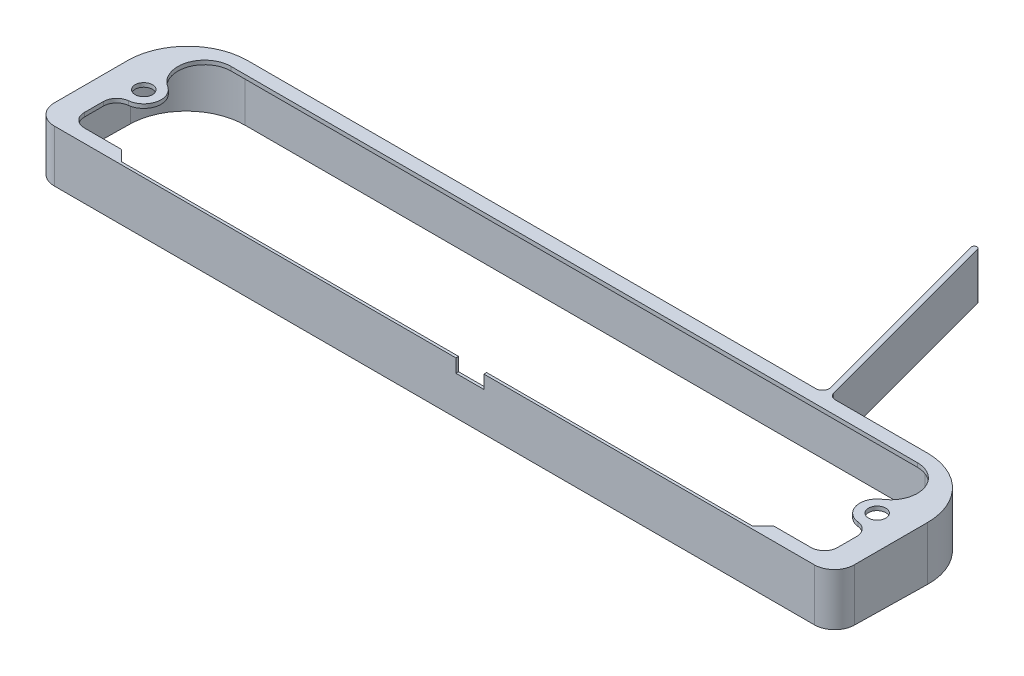
SolidWorks part; units mm, degrees
material "ABS"
ref_plane "Front" through (0, 0, 0) normal (0, 0, 1) x (1, 0, 0)
ref_plane "Top" through (0, 0, 0) normal (0, 1, 0) x (1, 0, 0)
ref_plane "Right" through (0, 0, 0) normal (1, 0, 0) x (0, 0, -1)
ref_axis "X" through (-80.9, 0, 0) along (1, 0, 0)
ref_axis "Y" through (0, -50, 0) along (0, 1, 0)
ref_axis "Z" through (0, 0, -80.9) along (0, 0, 1)
sketch "Sketch1" plane through (0, 0, 0) normal (0, 1, 0) x (1, 0, 0)
  line L0 (-57, 0) -> (-56.5, 0)
  line L2 (-51.4595, 21) -> (51.4595, 21)
  line L4 (56.5, 0) -> (57, 0)
  line L5 (60, 3) -> (60, 14)
  line L6 (51, 23) -> (-51, 23)
  line L7 (-60, 14) -> (-60, 3)
  line L8 (-56.5, 0) -> (56.5, 0)
  line L9 (-49, 0.4) -> (49, 0.4)
  line L10 (-56.5, 0) -> (-56.5, 0.4) construction
  line L11 (56.5, 0) -> (56.5, 0.4) construction
  line L12 (55, 11.43) -> (-55, 11.43) construction
  line L13 (0, 11.43) -> (0, 0) construction
  line L14 (56.5, 2) -> (49, 2)
  line L15 (49, 2) -> (49, 0.4)
  line L16 (-56.5, 2) -> (-49, 2)
  line L17 (-49, 2) -> (-49, 0.4)
  line L18 (-56.5, 0.4) -> (-56.5, 2) construction
  line L19 (-56.5, 0.4) -> (-49, 0.4) construction
  line L20 (56.5, 2) -> (56.5, 0.4) construction
  line L21 (49, 0.4) -> (56.5, 0.4) construction
  line L22 (56.5, 6.8573) -> (56.5, 2)
  line L23 (-56.5, 2) -> (-56.5, 6.8573)
  arc A0 (-53.6053, 13.6242) -> (-51.4595, 21) centre (-51.4595, 17) cw
  arc A1 (51.4595, 21) -> (53.6053, 13.6242) centre (51.4595, 17) cw
  arc A2 (60, 14) -> (51, 23) centre (51, 14) ccw
  arc A3 (-51, 23) -> (-60, 14) centre (-51, 14) ccw
  circle A4 centre (55, 11.43) radius 1.3
  circle A5 centre (-55, 11.43) radius 1.3
  arc A6 (53.6053, 13.6242) -> (54.7174, 8.8454) centre (55, 11.43) ccw
  arc A7 (-53.6053, 13.6242) -> (-54.7174, 8.8454) centre (-55, 11.43) cw
  arc A8 (-54.7174, 8.8454) -> (-56.5, 6.8573) centre (-54.5, 6.8573) ccw
  arc A9 (56.5, 6.8573) -> (54.7174, 8.8454) centre (54.5, 6.8573) ccw
  arc A10 (-57, 0) -> (-60, 3) centre (-57, 3) cw
  arc A11 (60, 3) -> (57, 0) centre (57, 3) cw
  dimension "D5" = 9
  dimension "D6" = 4
  dimension "D10" = 2.6
  dimension "D13" = 2.6
  dimension "D14" = 2
  dimension "D15" = 3
  dimension "D1" = 120
  dimension "D2" = 3.5
  dimension "D3" = 2
  dimension "D4" = 23
  dimension "D7" = 0.4
  dimension "D8" = 11.43
  dimension "D9" = 110
  dimension "D11" = 11
  dimension "D12" = 2
extrude "Boss-Extrude1" add sketch "Sketch1" along normal blind 0.6
sketch "Sketch8" plane through (0, 0, 0) normal (0, -1, 0) x (-1, 0, 0)
  line L4 (51, 22.6) -> (-51, 22.6)
  line L5 (-59.6, 14) -> (-59.6, 3)
  line L12 (-57, 0.4) -> (57, 0.4)
  line L13 (59.6, 3) -> (59.6, 14)
  line L14 (-57, 0) -> (57, 0)
  line L15 (60, 3) -> (60, 14)
  line L16 (51, 23) -> (-51, 23)
  line L17 (-60, 14) -> (-60, 3)
  line L18 (-57, 0) -> (57, 0)
  line L19 (60, 3) -> (60, 14)
  line L20 (51, 23) -> (-51, 23)
  line L21 (-60, 14) -> (-60, 3)
  arc A6 (-51, 22.6) -> (-59.6, 14) centre (-51, 14) ccw
  arc A7 (-59.6, 3) -> (-57, 0.4) centre (-57, 3) ccw
  arc A8 (57, 0.4) -> (59.6, 3) centre (57, 3) ccw
  arc A9 (59.6, 14) -> (51, 22.6) centre (51, 14) ccw
  arc A14 (-60, 3) -> (-57, 0) centre (-57, 3) ccw
  arc A15 (57, 0) -> (60, 3) centre (57, 3) ccw
  arc A16 (60, 14) -> (51, 23) centre (51, 14) ccw
  arc A17 (-51, 23) -> (-60, 14) centre (-51, 14) ccw
  arc A18 (-60, 3) -> (-57, 0) centre (-57, 3) ccw
  arc A19 (57, 0) -> (60, 3) centre (57, 3) ccw
  arc A20 (60, 14) -> (51, 23) centre (51, 14) ccw
  arc A21 (-51, 23) -> (-60, 14) centre (-51, 14) ccw
  dimension "D1" = 0
  dimension "D2" = 0.4
extrude "Boss-Extrude2" add sketch "Sketch8" along normal blind 8.2 from surface starting at face at (0, 0.6, -10.3107)
chamfer "Chamfer1" distance 0.6 angle 45 9 edges at (53, 0, -0.4) (-53, 0, -0.4) (58.8385, 0, -1.1615) (-58.8385, 0, -1.1615) (59.6, 0, -8.5) (-59.6, 0, -8.5) (57.0811, 0, -20.0811) (-57.0811, 0, -20.0811) (0, 0, -22.6)
sketch "Sketch9" plane through (0, 0, 0) normal (1, 0, 0) x (0, 0, -1)
  line L0 (-2, -7.6) -> (23, -7.6)
  line L1 (23, -7.6) -> (-2, -7.1636)
  line L3 (-2, -7.1636) -> (-2, -7.6)
  dimension "D1" = 25
  dimension "D2" = 1
extrude "Cut-Extrude1" cut sketch "Sketch9" against normal through all both and the other way through all
sketch "Sketch11" plane through (0, 0, 0) normal (0, 0, 1) x (1, 0, 0)
  line L0 (3.25, 0.6) -> (3.25, -1.4)
  line L1 (-57, 0.6) -> (57, 0.6) construction
  line L2 (3.25, -1.4) -> (7.45, -1.4)
  line L3 (7.45, -1.4) -> (7.45, 0.6)
  line L4 (7.45, 0.6) -> (3.25, 0.6)
  line L5 (5.35, -1.4) -> (5.35, 0.6) construction
  line L7 (60, 0.6) -> (60, -7.1985) construction
  dimension "D1" = 54.65
  dimension "D2" = 4.2
  dimension "D3" = 2
extrude "Cut-Extrude2" cut sketch "Sketch11" against normal up to next
fillet "Fillet1" radius 2 2 edges at (-56.5, 0.3, -2) (56.5, 0.3, -2)
chamfer "Chamfer2" distance 1.7 angle 45 2 edges at (-49, 0, -0.4) (49, 0, -0.4)
sketch "Sketch12" plane through (0, 0, 0) normal (0, 1, 0) x (1, 0, 0)
  line L1 (-57, 0) -> (57, 0) construction
  line L3 (-70.0161, 72.0463) -> (123.9526, 72.0463) construction
  line L10 (7.45, 0) -> (57, 0) construction
  line L11 (0, 38.0905) -> (0, 0) construction
  line L14 (28.2727, 53.2071) -> (36.3667, 23)
  line L30 (35.5385, 23) -> (27.5, 53)
  line L39 (35.5385, 23) -> (36.3667, 23)
  line L40 (51, 23) -> (-51, 23) construction
  arc A6 (27.5, 53) -> (28.2727, 53.2071) centre (27.8864, 53.1035) cw
  dimension "D3" = 72.0463
  dimension "D1" = 27.5
  dimension "D2" = 30
  dimension "D4" = 15
  dimension "D5" = 0.8
extrude "Boss-Extrude3" add sketch "Sketch12" against normal blind 7 from surface starting at face at (0.7643, 0.6, -7.1934)
fillet "Fillet2" radius 1 2 edges at (35.5385, -2.9, -23) (36.3667, -2.9, -23)
equation "\"D3@Sketch12\"=200-127.95373"
